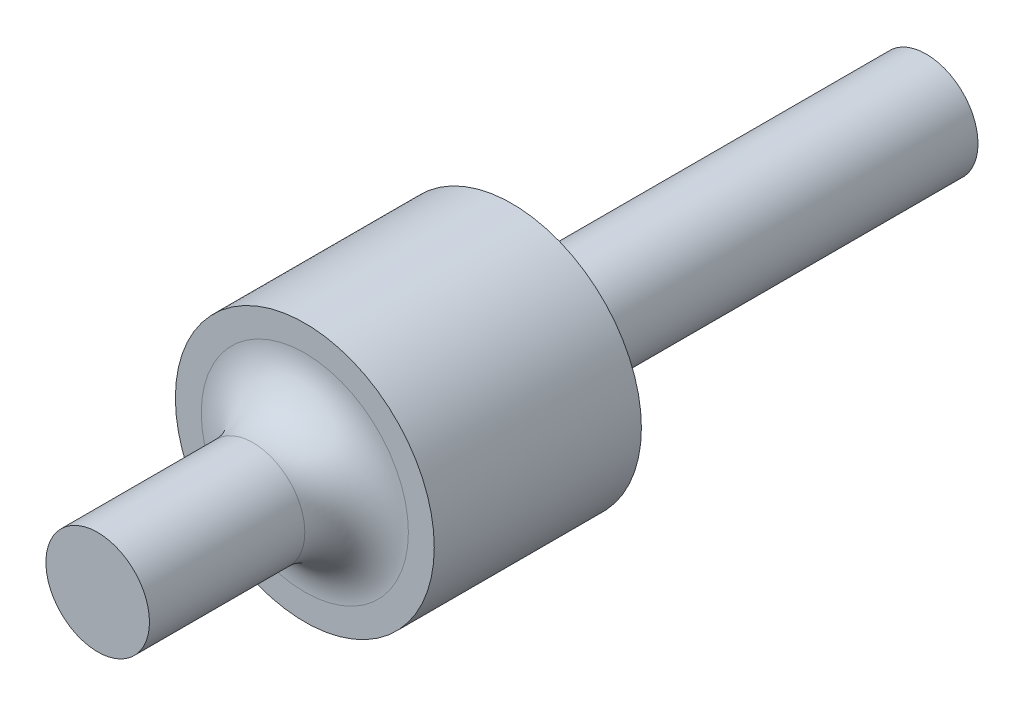
SolidWorks part; units mm, degrees
ref_plane "Front Plane" through (0, 0, 0) normal (0, 0, 1) x (1, 0, 0)
ref_plane "Top Plane" through (0, 0, 0) normal (0, 1, 0) x (1, 0, 0)
ref_plane "Right Plane" through (0, 0, 0) normal (1, 0, 0) x (0, 0, -1)
sketch "Sketch1" plane through (0, 0, 0) normal (0, 0, 1) x (1, 0, 0)
  circle A0 centre (0, 0) radius 12.5
extrude "Boss-Extrude1" add sketch "Sketch1" along normal mid plane 20
sketch "Sketch2" plane through (0, 0, 10) normal (0, 0, 1) x (1, 0, 0)
  circle A0 centre (0, 0) radius 5
extrude "Boss-Extrude2" add sketch "Sketch2" along normal blind 20
sketch "Sketch3" plane through (0, 0, -10) normal (0, 0, -1) x (-1, 0, 0)
  circle A0 centre (0, 0) radius 5
extrude "Boss-Extrude3" add sketch "Sketch3" along normal blind 40
fillet "Fillet1" radius 5 2 edges at (5, 0, 10) (-5, 0, -10)
